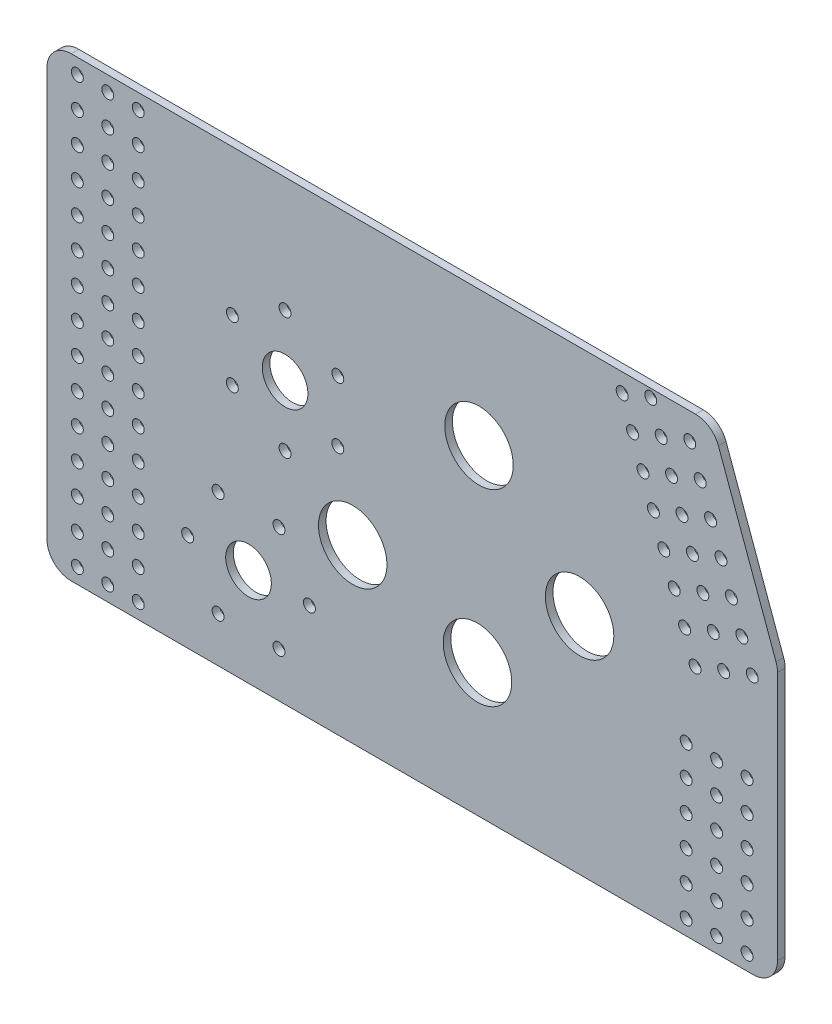
SolidWorks part; units mm, degrees
ref_plane "Front Plane" through (0, 0, 0) normal (0, 0, 1) x (1, 0, 0)
ref_plane "Top Plane" through (0, 0, 0) normal (0, 1, 0) x (1, 0, 0)
ref_plane "Right Plane" through (0, 0, 0) normal (1, 0, 0) x (0, 0, -1)
sketch "Sketch1" plane through (0, 0, 0) normal (0, 0, 1) x (1, 0, 0)
  line B0 (-152.4, 0) -> (152.4, 0)
  line B1 (152.4, 0) -> (152.4, 116.0843)
  line B2 (152.4, 116.0843) -> (125.3149, 190.5)
  line B3 (125.3149, 190.5) -> (-152.4, 190.5)
  line B4 (-152.4, 190.5) -> (-152.4, 0)
  circle B5 centre (-139.7, 184.15) radius 2.4892
  circle B6 centre (-127, 184.15) radius 2.4892
  circle B7 centre (-114.3, 184.15) radius 2.4892
  circle B8 centre (-127, 171.45) radius 2.4892
  circle B9 centre (-114.3, 171.45) radius 2.4892
  circle B10 centre (-127, 158.75) radius 2.4892
  circle B11 centre (-114.3, 158.75) radius 2.4892
  circle B12 centre (-127, 146.05) radius 2.4892
  circle B13 centre (-114.3, 146.05) radius 2.4892
  circle B14 centre (-127, 133.35) radius 2.4892
  circle B15 centre (-114.3, 133.35) radius 2.4892
  circle B16 centre (-127, 120.65) radius 2.4892
  circle B17 centre (-114.3, 120.65) radius 2.4892
  circle B18 centre (-127, 107.95) radius 2.4892
  circle B19 centre (-114.3, 107.95) radius 2.4892
  circle B20 centre (-127, 95.25) radius 2.4892
  circle B21 centre (-114.3, 95.25) radius 2.4892
  circle B22 centre (-127, 82.55) radius 2.4892
  circle B23 centre (-114.3, 82.55) radius 2.4892
  circle B24 centre (-127, 69.85) radius 2.4892
  circle B25 centre (-114.3, 69.85) radius 2.4892
  circle B26 centre (-127, 57.15) radius 2.4892
  circle B27 centre (-114.3, 57.15) radius 2.4892
  circle B28 centre (-127, 44.45) radius 2.4892
  circle B29 centre (-114.3, 44.45) radius 2.4892
  circle B30 centre (-127, 31.75) radius 2.4892
  circle B31 centre (-114.3, 31.75) radius 2.4892
  circle B32 centre (-127, 19.05) radius 2.4892
  circle B33 centre (-114.3, 19.05) radius 2.4892
  circle B34 centre (-127, 6.35) radius 2.4892
  circle B35 centre (-114.3, 6.35) radius 2.4892
  circle B36 centre (-139.7, 171.45) radius 2.4892
  circle B37 centre (-139.7, 158.75) radius 2.4892
  circle B38 centre (-139.7, 146.05) radius 2.4892
  circle B39 centre (-139.7, 133.35) radius 2.4892
  circle B40 centre (-139.7, 120.65) radius 2.4892
  circle B41 centre (-139.7, 107.95) radius 2.4892
  circle B42 centre (-139.7, 95.25) radius 2.4892
  circle B43 centre (-139.7, 82.55) radius 2.4892
  circle B44 centre (-139.7, 69.85) radius 2.4892
  circle B45 centre (-139.7, 57.15) radius 2.4892
  circle B46 centre (-139.7, 44.45) radius 2.4892
  circle B47 centre (-139.7, 31.75) radius 2.4892
  circle B48 centre (-139.7, 19.05) radius 2.4892
  circle B49 centre (-139.7, 6.35) radius 2.4892
  circle B50 centre (87.5907, 182.7494) radius 2.4892
  circle B51 centre (99.5248, 187.093) radius 2.4892
  circle B52 centre (115.8026, 179.5026) radius 2.4892
  circle B53 centre (91.9344, 170.8153) radius 2.4892
  circle B54 centre (103.8685, 175.1589) radius 2.4892
  circle B55 centre (120.1462, 167.5685) radius 2.4892
  circle B56 centre (96.278, 158.8812) radius 2.4892
  circle B57 centre (108.2121, 163.2248) radius 2.4892
  circle B58 centre (124.4899, 155.6344) radius 2.4892
  circle B59 centre (100.6217, 146.9471) radius 2.4892
  circle B60 centre (112.5558, 151.2907) radius 2.4892
  circle B61 centre (128.8335, 143.7003) radius 2.4892
  circle B62 centre (104.9653, 135.013) radius 2.4892
  circle B63 centre (116.8994, 139.3566) radius 2.4892
  circle B64 centre (133.1772, 131.7662) radius 2.4892
  circle B65 centre (109.309, 123.0789) radius 2.4892
  circle B66 centre (121.2431, 127.4226) radius 2.4892
  circle B67 centre (137.5208, 119.8321) radius 2.4892
  circle B68 centre (113.6526, 111.1448) radius 2.4892
  circle B69 centre (125.5867, 115.4885) radius 2.4892
  circle B70 centre (141.8645, 107.898) radius 2.4892
  circle B71 centre (117.9963, 99.2107) radius 2.4892
  circle B72 centre (129.9304, 103.5544) radius 2.4892
  circle B73 centre (146.2081, 95.9639) radius 2.4892
  circle B74 centre (114.3, 69.85) radius 2.4892
  circle B75 centre (127, 69.85) radius 2.4892
  circle B76 centre (139.7, 69.85) radius 2.4892
  circle B77 centre (114.3, 57.15) radius 2.4892
  circle B78 centre (127, 57.15) radius 2.4892
  circle B79 centre (139.7, 57.15) radius 2.4892
  circle B80 centre (114.3, 44.45) radius 2.4892
  circle B81 centre (127, 44.45) radius 2.4892
  circle B82 centre (139.7, 44.45) radius 2.4892
  circle B83 centre (114.3, 31.75) radius 2.4892
  circle B84 centre (127, 31.75) radius 2.4892
  circle B85 centre (139.7, 31.75) radius 2.4892
  circle B86 centre (114.3, 19.05) radius 2.4892
  circle B87 centre (127, 19.05) radius 2.4892
  circle B88 centre (139.7, 19.05) radius 2.4892
  circle B89 centre (114.3, 6.35) radius 2.4892
  circle B90 centre (127, 6.35) radius 2.4892
  circle B91 centre (139.7, 6.35) radius 2.4892
  circle B92 centre (11.8508, 132.0168) radius 14.2875
  circle B93 centre (-24.8197, 71.7449) radius 14.2875
  circle B94 centre (57.6351, 95.7125) radius 14.2875
  circle B95 centre (23.7546, 49.6787) radius 14.2875
  circle B96 centre (-65.2702, 36.9534) radius 9.525
  circle B97 centre (-65.2702, 106.5494) radius 9.525
  circle B98 centre (-65.2702, 131.9494) radius 2.4892
  circle B99 centre (-65.2702, 11.5534) radius 2.4892
  circle B100 centre (-43.2731, 119.2494) radius 2.4892
  circle B101 centre (-43.2731, 93.8494) radius 2.4892
  circle B102 centre (-65.2702, 81.1494) radius 2.4892
  circle B103 centre (-87.2672, 93.8494) radius 2.4892
  circle B104 centre (-87.2672, 119.2494) radius 2.4892
  circle B105 centre (-87.2672, 24.2534) radius 2.4892
  circle B106 centre (-87.2672, 49.6534) radius 2.4892
  circle B107 centre (-65.2702, 62.3534) radius 2.4892
  circle B108 centre (-43.2731, 49.6534) radius 2.4892
  circle B109 centre (-43.2731, 24.2534) radius 2.4892
sketch_block_instance "Block-InnerPlate-1"
sketch_block "Block-InnerPlate" parameters "D1"=4.9784, "D7"=4.9784, "D8"=4.9784, "D9"=4.9784, "D11"=4.9784, "D12"=4.9784, "D13"=4.9784, "D15"=19.05, "D16"=19.05, "D17"=28.575, "D18"=28.575, "D19"=28.575, "D20"=28.575, "D21"=4.9784, "D22"=4.9784, "D2"=6.35, "D3"=12.7, "D4"=12.7, "D5"=12.7, "D6"=6.35, "D10"=12.7, "D14"=12.7, "D23"=25.4, "D24"=25.4
extrude "Boss-Extrude1" add sketch "Sketch1" along normal blind 3.175
sketch "Sketch2" plane through (0, 0, 3.175) normal (0, 0, 1) x (1, 0, 0)
  circle A0 centre (146.2081, 95.9639) radius 2.4892
  dimension "D1" = 4.9784
extrude "Boss-Extrude2" add sketch "Sketch2" against normal blind 3.175
fillet "Fillet1" radius 10.16 5 edges at (-152.4, 0, 1.5875) (152.4, 0, 1.5875) (152.4, 116.0843, 1.5875) (125.3149, 190.5, 1.5875) (-152.4, 190.5, 1.5875)
sketch "Sketch3" plane through (0, 0, 3.175) normal (0, 0, 1) x (1, 0, 0)
  line L0 (-65.2702, 106.5494) -> (-39.8702, 106.5494) construction
  line L1 (-65.2702, 36.9534) -> (-39.8702, 36.9534) construction
  circle A0 centre (-65.2702, 106.5494) radius 9.525
  circle A1 centre (-39.8702, 106.5494) radius 2.4892
  circle A2 centre (-52.5702, 84.5524) radius 2.4892
  circle A3 centre (-77.9702, 84.5524) radius 2.4892
  circle A4 centre (-90.6702, 106.5494) radius 2.4892
  circle A5 centre (-77.9702, 128.5465) radius 2.4892
  circle A6 centre (-52.5702, 128.5465) radius 2.4892
  circle A7 centre (-65.2702, 36.9534) radius 9.525
  circle A8 centre (-39.8702, 36.9534) radius 2.4892
  circle A9 centre (-52.5702, 14.9564) radius 2.4892
  circle A10 centre (-77.9702, 14.9564) radius 2.4892
  circle A11 centre (-90.6702, 36.9534) radius 2.4892
  circle A12 centre (-77.9702, 58.9505) radius 2.4892
  circle A13 centre (-52.5702, 58.9505) radius 2.4892
  dimension "D1" = 19.05
  dimension "D2" = 4.9784
  dimension "D7" = 19.05
  dimension "D8" = 4.9784
  dimension "D3" = 25.4
  dimension "D5" = 25.4
  dimension "D6" = 25.4
  dimension "D9" = 25.4
  dimension "D11" = 25.4
  dimension "D4" = 6
  dimension "D10" = 6
extrude "Cut-Extrude1" cut sketch "Sketch3" against normal blind 3.175
sketch "Sketch4" plane through (0, 0, 3.175) normal (0, 0, 1) x (1, 0, 0)
  circle A0 centre (-65.2702, 131.9494) radius 2.4892
  circle A1 centre (-43.2731, 119.2494) radius 2.4892
  circle A2 centre (-43.2731, 93.8494) radius 2.4892
  circle A3 centre (-65.2702, 81.1494) radius 2.4892
  circle A4 centre (-87.2672, 93.8494) radius 2.4892
  circle A5 centre (-87.2672, 119.2494) radius 2.4892
  circle A6 centre (-65.2702, 62.3534) radius 2.4892
  circle A7 centre (-43.2731, 49.6534) radius 2.4892
  circle A8 centre (-43.2731, 24.2534) radius 2.4892
  circle A9 centre (-65.2702, 11.5534) radius 2.4892
  circle A10 centre (-87.2672, 24.2534) radius 2.4892
  circle A11 centre (-87.2672, 49.6534) radius 2.4892
  dimension "D1" = 4.9784
  dimension "D2" = 4.9784
  dimension "D3" = 4.9784
  dimension "D4" = 4.9784
  dimension "D5" = 4.9784
  dimension "D6" = 4.9784
  dimension "D7" = 4.9784
  dimension "D8" = 4.9784
  dimension "D9" = 4.9784
  dimension "D10" = 4.9784
  dimension "D11" = 4.9784
  dimension "D12" = 4.9784
extrude "Boss-Extrude3" add sketch "Sketch4" against normal blind 3.175
sketch "Sketch6" plane through (0, 0, 3.175) normal (0, 0, 1) x (1, 0, 0)
  circle A0 centre (23.7546, 49.6787) radius 14.2875 construction
  circle A1 centre (57.6351, 95.7125) radius 14.2875 construction
  circle A2 centre (11.8508, 132.0168) radius 14.2875 construction
  circle A3 centre (23.7546, 49.6787) radius 14.2875
  circle A4 centre (57.6351, 95.7125) radius 14.2875
  circle A5 centre (11.8508, 132.0168) radius 14.2875
  circle A6 centre (-39.8702, 36.9534) radius 2.4892 construction
  circle A7 centre (-52.5702, 14.9564) radius 2.4892 construction
  circle A8 centre (-77.9702, 14.9564) radius 2.4892 construction
  circle A9 centre (-65.2702, 36.9534) radius 9.525 construction
  circle A10 centre (-90.6702, 36.9534) radius 2.4892 construction
  circle A11 centre (-52.5702, 58.9505) radius 2.4892 construction
  circle A12 centre (-77.9702, 58.9505) radius 2.4892 construction
  circle A13 centre (-52.5702, 84.5524) radius 2.4892 construction
  circle A14 centre (-77.9702, 84.5524) radius 2.4892 construction
  circle A15 centre (-90.6702, 106.5494) radius 2.4892 construction
  circle A16 centre (-65.2702, 106.5494) radius 9.525 construction
  circle A17 centre (-39.8702, 106.5494) radius 2.4892 construction
  circle A18 centre (-52.5702, 128.5465) radius 2.4892 construction
  circle A19 centre (-77.9702, 128.5465) radius 2.4892 construction
  circle A20 centre (-39.8702, 36.9534) radius 2.4892
  circle A21 centre (-52.5702, 14.9564) radius 2.4892
  circle A22 centre (-77.9702, 14.9564) radius 2.4892
  circle A23 centre (-65.2702, 36.9534) radius 9.525
  circle A24 centre (-90.6702, 36.9534) radius 2.4892
  circle A25 centre (-52.5702, 58.9505) radius 2.4892
  circle A26 centre (-77.9702, 58.9505) radius 2.4892
  circle A27 centre (-52.5702, 84.5524) radius 2.4892
  circle A28 centre (-77.9702, 84.5524) radius 2.4892
  circle A29 centre (-90.6702, 106.5494) radius 2.4892
  circle A30 centre (-65.2702, 106.5494) radius 9.525
  circle A31 centre (-39.8702, 106.5494) radius 2.4892
  circle A32 centre (-52.5702, 128.5465) radius 2.4892
  circle A33 centre (-77.9702, 128.5465) radius 2.4892
extrude "Boss-Extrude4" add sketch "Sketch6" against normal up to surface (3.175 mm away) up to face at (-37.381, 36.9534, 0)
sketch "Sketch5" plane through (0, 0, 3.175) normal (0, 0, 1) x (1, 0, 0)
  circle A1 centre (-24.8197, 71.7449) radius 14.2875
  circle A2 centre (-24.8197, 71.7449) radius 13.97
  circle A3 centre (27.2348, 55.2349) radius 40.64
  circle A4 centre (27.2348, 55.2349) radius 14.2875
  circle A5 centre (27.2348, 55.2349) radius 22.86
  circle A6 centre (69.8319, 93.3349) radius 34.29
  circle A7 centre (69.8319, 93.3349) radius 14.2875
  circle A8 centre (69.8319, 93.3349) radius 12.7
  circle A9 centre (27.8642, 133.9749) radius 45.72
  circle A10 centre (27.8642, 133.9749) radius 14.2875
  circle A11 centre (-24.8197, 71.7449) radius 14.2875 construction
  dimension "D1" = 27.94
  dimension "D2" = 81.28
  dimension "D3" = 28.575
  dimension "D4" = 45.72
  dimension "D5" = 68.58
  dimension "D6" = 28.575
  dimension "D7" = 25.4
  dimension "D8" = 91.44
  dimension "D12" = 28.575
  dimension "D9" = 16.51
  dimension "D10" = 38.1
  dimension "D11" = 40.64
extrude "Cut-Extrude2" cut sketch "Sketch5" against normal through all contours A4 | A9 A7 A8 | A8 | A7 A9 | A10 region at (69.8319, 93.3349, 3.175) region at (58.9004, 99.8547, 3.175) region at (60.198, 102.664, 3.175) region at (27.2348, 55.2349, 3.175) region at (27.8642, 133.9749, 3.175)
sketch "Sketch7" plane through (0, 0, 0) normal (0, 0, 1) x (1, 0, 0)
  circle A0 centre (-55.5743, 18.8147) radius 2.4892
  circle A1 centre (-24.8197, 71.7449) radius 14.2875
  circle A2 centre (-24.8197, 71.7449) radius 45.72 construction
  circle A3 centre (-53.0343, 117.0118) radius 7.62 construction
  circle A4 centre (-24.8197, 71.7449) radius 14.2875 construction
  circle A5 centre (-68.2743, 40.8118) radius 7.62 construction
  circle A6 centre (-53.0343, 117.0118) radius 32.5374 construction
  circle A7 centre (-80.9743, 18.8147) radius 2.4892
  circle A8 centre (-68.2743, 40.8118) radius 32.5374 construction
  circle A9 centre (-93.6743, 40.8118) radius 2.4892
  circle A10 centre (-68.2743, 40.8118) radius 9.525
  circle A11 centre (-42.8743, 40.8118) radius 2.4892
  circle A12 centre (-55.5743, 62.8088) radius 2.4892
  circle A13 centre (-80.9743, 62.8088) radius 2.4892
  circle A14 centre (-31.0373, 104.3118) radius 2.4892
  circle A15 centre (-53.0343, 91.6118) radius 2.4892
  circle A16 centre (-75.0314, 104.3118) radius 2.4892
  circle A17 centre (-53.0343, 117.0118) radius 9.525
  circle A18 centre (-31.0373, 129.7118) radius 2.4892
  circle A19 centre (-53.0343, 142.4118) radius 2.4892
  circle A20 centre (-75.0314, 129.7118) radius 2.4892
  dimension "D1" = 91.44
  dimension "D2" = 15.24
  dimension "D5" = 65.0748
  dimension "D6" = 65.0748
  dimension "D7" = 19.05
  dimension "D8" = 4.9784
  dimension "D9" = 25.4
  dimension "D10" = 25.4
  dimension "D11" = 25.4
  dimension "D14" = 25.4
  dimension "D15" = 25.4
  dimension "D16" = 25.4
  dimension "D17" = 25.4
  dimension "D18" = 25.4
  dimension "D19" = 19.05
  dimension "D20" = 4.9784
  dimension "D3" = 76.2
  dimension "D4" = 15.24
  dimension "D12" = 25.4
  dimension "D13" = 25.4
  dimension "D21" = 25.4
  dimension "D22" = 25.4
  dimension "D23" = 25.4
  dimension "D24" = 25.4
  dimension "D25" = 25.4
  dimension "D26" = 25.4
  dimension "D27" = 25.4
  dimension "D28" = 25.4
  dimension "D29" = 25.4
  dimension "D30" = 25.4
  dimension "D31" = 25.4
extrude "Cut-Extrude3" cut sketch "Sketch7" along normal through all contours A9 | A13 | A11 | A12 | A7 | A0 | A10 | A20 | A17 | A19 | A15 | A14 | A18 | A16 region at (-55.5743, 18.8147, 0) region at (-80.9743, 18.8147, 0) region at (-93.6743, 40.8118, 0) region at (-68.2743, 40.8118, 0) region at (-42.8743, 40.8118, 0) region at (-55.5743, 62.8088, 0) region at (-80.9743, 62.8088, 0) region at (-31.0373, 104.3118, 0) region at (-53.0343, 91.6118, 0) region at (-53.0343, 117.0118, 0) region at (-31.0373, 129.7118, 0) region at (-53.0343, 142.4118, 0) region at (-75.0314, 129.7118, 0)
